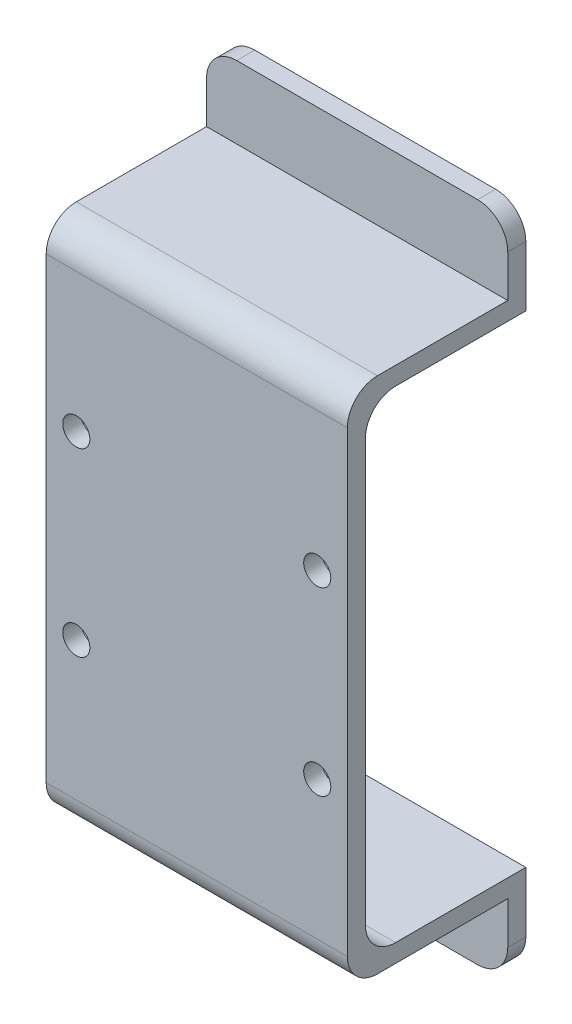
SolidWorks part; units mm, degrees
ref_plane "Alzado" through (0, 0, 0) normal (0, 0, 1) x (1, 0, 0)
ref_plane "Planta" through (0, 0, 0) normal (0, 1, 0) x (1, 0, 0)
ref_plane "Vista lateral" through (0, 0, 0) normal (1, 0, 0) x (0, 0, -1)
sketch "Croquis1" plane through (0, 0, 0) normal (0, 0, 1) x (1, 0, 0)
  line L0 (126.8935, -155) -> (126.8935, -375) construction
  line L1 (26.8935, -345) -> (126.8935, -345)
  line L2 (26.8935, -345) -> (26.8935, -365)
  line L3 (36.8935, -375) -> (116.8935, -375)
  line L4 (126.8935, -345) -> (126.8935, -365)
  line L5 (126.8935, -155) -> (126.8935, -375) construction
  line L14 (26.8935, -375) -> (126.8935, -375) construction
  line L17 (26.8935, -155) -> (26.8935, -375) construction
  line L20 (26.8935, -155) -> (26.8935, -375) construction
  line L21 (26.8935, -265) -> (126.8935, -265) construction
  line L22 (36.8935, -155) -> (116.8935, -155)
  line L23 (126.8935, -185) -> (126.8935, -165)
  line L24 (26.8935, -185) -> (126.8935, -185)
  line L25 (26.8935, -185) -> (26.8935, -165)
  arc A0 (116.8935, -155) -> (126.8935, -165) centre (116.8935, -165) cw
  arc A1 (116.8935, -375) -> (126.8935, -365) centre (116.8935, -365) ccw
  arc A2 (36.8935, -375) -> (26.8935, -365) centre (36.8935, -365) cw
  arc A9 (36.8935, -155) -> (26.8935, -165) centre (36.8935, -165) ccw
  dimension "D1" = 10
  dimension "D2" = 30
  dimension "D3" = 100
extrude "Saliente-Extruir1" add sketch "Croquis1" along normal blind 6
sketch "Croquis3" plane through (0, 0, 6) normal (0, 0, 1) x (1, 0, 0)
  line L12 (126.8935, -365) -> (126.8935, -345) construction
  line L17 (26.8935, -345) -> (126.8935, -345)
  line L18 (26.8935, -345) -> (26.8935, -351)
  line L31 (26.8935, -351) -> (126.8935, -351)
  line L32 (126.8935, -345) -> (126.8935, -351)
  line L33 (126.8935, -155) -> (126.8935, -375) construction
  line L34 (126.8935, -155) -> (126.8935, -375) construction
  line L35 (26.8935, -155) -> (26.8935, -375) construction
  line L36 (26.8935, -155) -> (26.8935, -375) construction
  line L37 (26.8935, -265) -> (126.8935, -265) construction
  line L38 (26.8935, -179) -> (126.8935, -179)
  line L39 (126.8935, -185) -> (126.8935, -179)
  line L40 (26.8935, -185) -> (126.8935, -185)
  line L41 (26.8935, -185) -> (26.8935, -179)
  dimension "D1" = 6
extrude "Saliente-Extruir2" add sketch "Croquis3" along normal blind 47.25
sketch "Croquis4" plane through (0, 0, 53.25) normal (0, 0, 1) x (1, 0, 0)
  line L0 (126.8935, -179) -> (26.8935, -179) construction
  line L1 (26.8935, -179) -> (126.8935, -179)
  line L2 (26.8935, -179) -> (26.8935, -351)
  line L3 (26.8935, -351) -> (126.8935, -351)
  line L4 (126.8935, -179) -> (126.8935, -351)
  line L5 (26.8935, -179) -> (26.8935, -185) construction
extrude "Saliente-Extruir3" add sketch "Croquis4" along normal blind 6
fillet "Redondeo1" radius 10 4 edges at (76.8935, -351, 59.25) (76.8935, -345, 53.25) (76.8935, -179, 59.25) (76.8935, -185, 53.25)
sketch "Croquis5" plane through (0, 0, 59.25) normal (0, 0, 1) x (1, 0, 0)
  arc A4 (33.3796, -292.1889) -> (40.4074, -297.8111) centre (36.8935, -295) ccw construction
  arc A5 (113.3796, -297.8111) -> (120.4074, -292.1889) centre (116.8935, -295) ccw construction
  arc A6 (40.4074, -232.1889) -> (33.3796, -237.8111) centre (36.8935, -235) ccw construction
  arc A7 (120.4074, -237.8111) -> (113.3796, -232.1889) centre (116.8935, -235) ccw construction
  arc A12 (33.3796, -292.1889) -> (40.4074, -297.8111) centre (36.8935, -295) ccw construction
  arc A13 (113.3796, -297.8111) -> (120.4074, -292.1889) centre (116.8935, -295) ccw construction
  arc A14 (40.4074, -232.1889) -> (33.3796, -237.8111) centre (36.8935, -235) ccw construction
  arc A15 (120.4074, -237.8111) -> (113.3796, -232.1889) centre (116.8935, -235) ccw construction
  circle A16 centre (36.8935, -235) radius 4.5
  circle A17 centre (116.8935, -235) radius 4.5
  circle A18 centre (36.8935, -295) radius 4.5
  circle A19 centre (116.8935, -295) radius 4.5
extrude "Cortar-Extruir1" cut sketch "Croquis5" against normal through all
equation "\"Grosor\"= 6mm"
equation "\"D1@Saliente-Extruir1\"=\"Grosor\""
equation "\"D1@Saliente-Extruir3\"=\"Grosor\""
